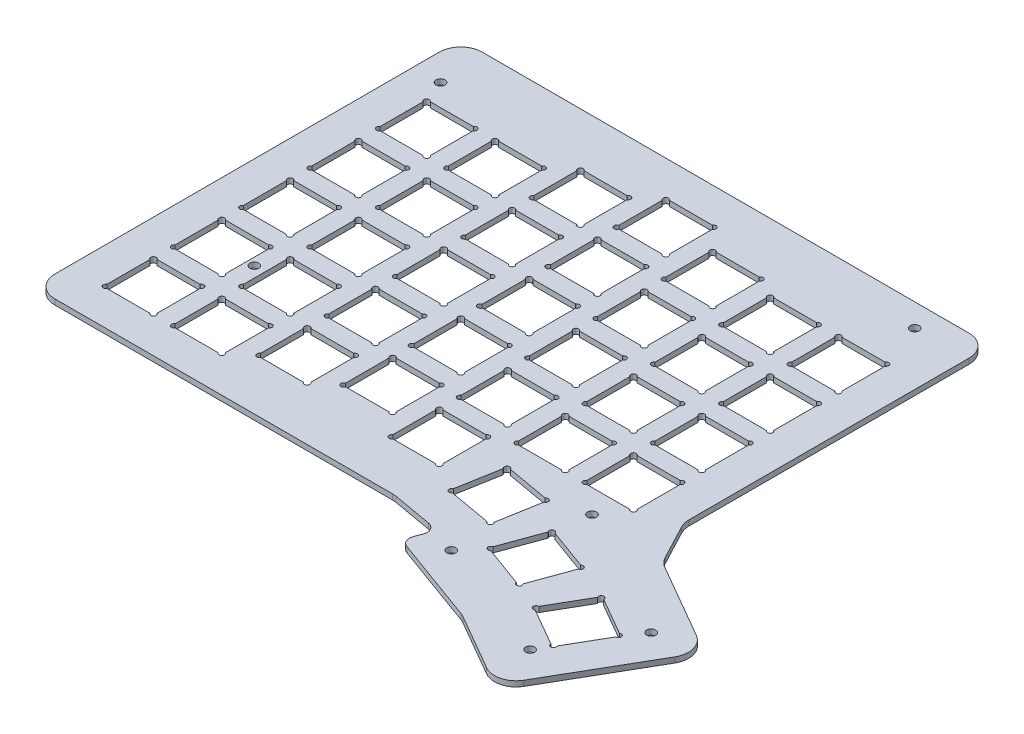
SolidWorks part; units mm, degrees
ref_plane "Front Plane" through (0, 0, 0) normal (0, 0, 1) x (1, 0, 0)
ref_plane "Top Plane" through (0, 0, 0) normal (0, 1, 0) x (1, 0, 0)
ref_plane "Right Plane" through (0, 0, 0) normal (1, 0, 0) x (0, 0, -1)
sketch "Sketch1" plane through (0, 0, 0) normal (0, 1, 0) x (1, 0, 0)
  line L0 (-118.7762, 124.6491) -> (29.0238, 124.6491)
  line L3 (35.6333, 26.5266) -> (63.1524, 10.6384)
  line L4 (63.1524, 10.6384) -> (41.7463, -26.4382)
  line L5 (41.7463, -26.4382) -> (20.3874, -14.1066)
  line L6 (20.3874, -14.1066) -> (-6.2441, -4.4135)
  line L7 (-6.2441, -4.4135) -> (-3.5838, 2.8955)
  line L8 (-3.5838, 2.8955) -> (-18.0659, 5.4491)
  line L9 (-18.0659, 5.4491) -> (-118.7762, 5.4491)
  line L10 (-118.7762, 5.4491) -> (-118.7762, 124.6491)
  line L11 (-17.8035, 8.4491) -> (-111.5762, 8.4491) construction
  line L12 (35.6333, 26.5266) -> (29.0238, 39.0847)
  line L13 (29.0238, 39.0847) -> (29.0238, 124.6491)
  line L14 (36.711, -20.067) -> (21.6594, -11.3769) construction
  line L15 (28.8016, 30.5418) -> (32.8015, 22.9418) construction
  line L16 (-115.7762, 12.6491) -> (-115.7762, 117.4491) construction
  line L17 (56.9174, 5.8389) -> (42.5399, -19.0636) construction
  line L18 (-111.5762, 121.6491) -> (22.8238, 121.6491) construction
  line L19 (30.0238, 26.4491) -> (55.6238, 11.5491) construction
  line L20 (26.0238, 118.4491) -> (26.0239, 34.0491) construction
  line L21 (26.0239, 34.0491) -> (30.0238, 26.4491) construction
  line L29 (21.6594, -11.3769) -> (1.2238, -3.9509) construction
  dimension "D9" = 3
  dimension "D4" = 3
  dimension "D7" = 20
  dimension "D5" = 10
  dimension "D8" = 30
  dimension "D3" = 3
  dimension "D2" = 3
  dimension "D10" = 3
  dimension "D11" = 3
  dimension "D6" = 3
  dimension "D12" = 3
  dimension "D13" = 3
  dimension "D14" = 5
  dimension "D15" = 3
extrude "Boss-Extrude1" add sketch "Sketch1" against normal blind 1.5
sketch "Sketch2" plane through (0, 0, 0) normal (0, 1, 0) x (1, 0, 0)
  line L0 (-37.8882, 114.9491) -> (-51.8882, 100.9491) construction
  line L1 (-51.8882, 114.9491) -> (-37.8882, 114.9491)
  line L2 (-51.8882, 114.9491) -> (-51.8882, 100.9491)
  line L3 (-51.8882, 100.9491) -> (-37.8882, 100.9491)
  line L4 (-37.8882, 114.9491) -> (-37.8882, 100.9491)
  line L5 (-51.8882, 114.9491) -> (-37.8882, 100.9491) construction
  line L6 (29.0238, 124.6491) -> (-118.7762, 124.6491) construction
  line L7 (-118.7762, 124.6491) -> (-118.7762, 5.4491) construction
  line L8 (-51.8882, 114.9491) -> (-52.065, 115.1259) construction
  line L9 (-51.5346, 114.5956) -> (-51.8882, 113.9341) construction
  line L10 (-51.5346, 114.5956) -> (-50.8732, 114.9491) construction
  circle A0 centre (-38.2418, 114.5956) radius 0.75
  circle A1 centre (-51.5346, 114.5956) radius 0.75
  circle A2 centre (-51.7114, 101.1259) radius 0.75
  circle A3 centre (-38.2418, 101.3027) radius 0.75
  dimension "D5" = 1.5
  dimension "D7" = 1.5
  dimension "D9" = 1.5
  dimension "D11" = 1.5
  dimension "D1" = 14
  dimension "D3" = 9.7
  dimension "D2" = 66.888
  dimension "D4" = 0.5
  dimension "D6" = 0.5
  dimension "D8" = 0.25
  dimension "D10" = 0.5
extrude "Cut-Extrude1" cut sketch "Sketch2" against normal blind 10 contours A3 L4 A0 L1 A1 L2 A2 L3 | A1 | A0 | A3 | A2 region at (-44.8994, 0, -107.9379)
sketch "Sketch3" plane through (0, 0, 0) normal (0, 1, 0) x (1, 0, 0)
  line L0 (-38.9032, 114.9491) -> (-50.8732, 114.9491) construction
  line L1 (-70.9383, 110.1866) -> (-56.9381, 110.1866)
  line L2 (-70.9383, 110.1866) -> (-70.9383, 96.1865)
  line L3 (-70.9383, 96.1865) -> (-56.9381, 96.1865)
  line L4 (-56.9381, 110.1866) -> (-56.9381, 96.1865)
  line L5 (-70.9383, 110.1866) -> (-56.9381, 96.1865) construction
  line L7 (-56.9381, 110.1866) -> (-70.9383, 96.1865) construction
  line L8 (-51.8882, 107.8944) -> (-37.8882, 107.9491) construction
  line L9 (-51.8882, 113.9341) -> (-51.8882, 101.8548) construction
  line L10 (-37.8882, 113.9341) -> (-37.8882, 101.9641) construction
  circle A0 centre (-57.2917, 109.8331) radius 0.75
  circle A1 centre (-70.5847, 109.8331) radius 0.75
  circle A2 centre (-70.5847, 96.5401) radius 0.75
  circle A3 centre (-57.2917, 96.5401) radius 0.75
  point P6 (-44.8882, 114.9491)
  point P7 (-63.9382, 110.1866)
  dimension "D7" = 1.5
  dimension "D9" = 1.5
  dimension "D4" = 0.5
  dimension "D6" = 0.5
  dimension "D8" = 1.5
  dimension "D10" = 1.5
  dimension "D1" = 19.05
  dimension "D2" = 4.7625
  dimension "D3" = 0.5
  dimension "D5" = 0.5
sketch "Sketch4" plane through (0, 0, 0) normal (0, 1, 0) x (1, 0, 0)
  line L0 (-38.9032, 114.9491) -> (-50.8732, 114.9491) construction
  line L1 (-89.9883, 105.4241) -> (-75.9881, 105.4241)
  line L2 (-89.9883, 105.4241) -> (-89.9883, 91.424)
  line L3 (-89.9883, 91.424) -> (-75.9881, 91.424)
  line L4 (-75.9881, 105.4241) -> (-75.9881, 91.424)
  line L5 (-56.9381, 110.1866) -> (-56.9381, 96.1865) construction
  line L6 (-89.9883, 105.4241) -> (-75.9881, 91.424) construction
  line L7 (-75.9881, 105.4241) -> (-89.9883, 91.424) construction
  line L8 (-51.8882, 107.8944) -> (-37.8882, 107.9491) construction
  line L9 (-51.8882, 113.9341) -> (-51.8882, 101.8548) construction
  line L10 (-37.8882, 113.9341) -> (-37.8882, 101.9641) construction
  circle A0 centre (-76.3417, 105.0706) radius 0.75
  circle A1 centre (-89.6347, 105.0706) radius 0.75
  circle A2 centre (-89.6347, 91.7776) radius 0.75
  circle A3 centre (-76.3417, 91.7776) radius 0.75
  dimension "D7" = 1.5
  dimension "D9" = 1.5
  dimension "D4" = 0.5
  dimension "D6" = 0.5
  dimension "D8" = 1.5
  dimension "D10" = 1.5
  dimension "D3" = 0.5
  dimension "D5" = 0.5
  dimension "D1" = 9.525
  dimension "D2" = 19.05
sketch "Sketch5" plane through (0, 0, 0) normal (0, 1, 0) x (1, 0, 0)
  line L0 (-38.9032, 114.9491) -> (-50.8732, 114.9491) construction
  line L1 (-109.0383, 105.4241) -> (-95.0381, 105.4241)
  line L2 (-109.0383, 105.4241) -> (-109.0383, 91.424)
  line L3 (-109.0383, 91.424) -> (-95.0381, 91.424)
  line L4 (-95.0381, 105.4241) -> (-95.0381, 91.424)
  line L5 (-75.9881, 105.4241) -> (-75.9881, 91.424) construction
  line L6 (-109.0383, 105.4241) -> (-95.0381, 91.424) construction
  line L8 (-95.0381, 105.4241) -> (-109.0383, 91.424) construction
  line L9 (-51.8882, 107.8944) -> (-37.8882, 107.9491) construction
  line L10 (-51.8882, 113.9341) -> (-51.8882, 101.8548) construction
  line L11 (-37.8882, 113.9341) -> (-37.8882, 101.9641) construction
  circle A0 centre (-108.6847, 105.0706) radius 0.75
  circle A1 centre (-95.3917, 105.0706) radius 0.75
  circle A2 centre (-95.3917, 91.7776) radius 0.75
  circle A3 centre (-108.6847, 91.7776) radius 0.75
  dimension "D7" = 1.5
  dimension "D9" = 1.5
  dimension "D4" = 0.5
  dimension "D6" = 0.5
  dimension "D8" = 1.5
  dimension "D10" = 1.5
  dimension "D1" = 19.05
  dimension "D3" = 0.5
  dimension "D5" = 0.5
  dimension "D2" = 9.525
sketch "Sketch6" plane through (0, 0, 0) normal (0, 1, 0) x (1, 0, 0)
  line L0 (-38.9032, 114.9491) -> (-50.8732, 114.9491) construction
  line L1 (-32.8382, 108.9491) -> (-18.8381, 108.9491)
  line L2 (-32.8382, 108.9491) -> (-32.8382, 94.949)
  line L3 (-32.8382, 94.949) -> (-18.8381, 94.949)
  line L4 (-18.8381, 108.9491) -> (-18.8381, 94.949)
  line L5 (-51.8882, 113.9341) -> (-51.8882, 101.8548) construction
  line L6 (-32.8382, 108.9491) -> (-18.8381, 94.949) construction
  line L7 (-18.8381, 108.9491) -> (-32.8382, 94.949) construction
  line L8 (-51.8882, 107.8944) -> (-37.8882, 107.9491) construction
  line L9 (-51.8882, 113.9341) -> (-51.8882, 101.8548) construction
  line L10 (-37.8882, 113.9341) -> (-37.8882, 101.9641) construction
  circle A0 centre (-32.4846, 108.5956) radius 0.75
  circle A1 centre (-19.1916, 108.5956) radius 0.75
  circle A2 centre (-32.4846, 95.3026) radius 0.75
  circle A3 centre (-19.1916, 95.3026) radius 0.75
  dimension "D7" = 1.5
  dimension "D9" = 1.5
  dimension "D4" = 0.5
  dimension "D6" = 0.5
  dimension "D8" = 1.5
  dimension "D10" = 1.5
  dimension "D3" = 0.5
  dimension "D5" = 0.5
  dimension "D2" = 19.05
  dimension "D1" = 6
sketch "Sketch7" plane through (0, 0, 0) normal (0, 1, 0) x (1, 0, 0)
  line L0 (-38.9032, 114.9491) -> (-50.8732, 114.9491) construction
  line L1 (-13.7882, 105.9491) -> (0.2119, 105.9491)
  line L2 (-13.7882, 105.9491) -> (-13.7882, 91.949)
  line L3 (-13.7882, 91.949) -> (0.2119, 91.949)
  line L4 (0.2119, 105.9491) -> (0.2119, 91.949)
  line L5 (-32.8382, 108.9491) -> (-32.8382, 94.949) construction
  line L6 (-13.7882, 105.9491) -> (0.2119, 91.949) construction
  line L7 (0.2119, 105.9491) -> (-13.7882, 91.949) construction
  line L8 (-51.8882, 107.8944) -> (-37.8882, 107.9491) construction
  line L9 (-51.8882, 113.9341) -> (-51.8882, 101.8548) construction
  line L10 (-37.8882, 113.9341) -> (-37.8882, 101.9641) construction
  circle A0 centre (-13.4346, 105.5956) radius 0.75
  circle A1 centre (-0.1416, 105.5956) radius 0.75
  circle A2 centre (-0.1416, 92.3026) radius 0.75
  circle A3 centre (-13.4346, 92.3026) radius 0.75
  dimension "D7" = 1.5
  dimension "D9" = 1.5
  dimension "D4" = 0.5
  dimension "D6" = 0.5
  dimension "D8" = 1.5
  dimension "D10" = 1.5
  dimension "D3" = 0.5
  dimension "D5" = 0.5
  dimension "D2" = 19.05
  dimension "D1" = 9
sketch "Sketch8" plane through (0, 0, 0) normal (0, 1, 0) x (1, 0, 0)
  line L0 (-38.9032, 114.9491) -> (-50.8732, 114.9491) construction
  line L1 (5.2618, 105.9491) -> (19.2619, 105.9491)
  line L2 (5.2618, 105.9491) -> (5.2618, 91.949)
  line L3 (5.2618, 91.949) -> (19.2619, 91.949)
  line L4 (19.2619, 105.9491) -> (19.2619, 91.949)
  line L5 (-13.7882, 105.9491) -> (-13.7882, 91.949) construction
  line L6 (5.2618, 105.9491) -> (19.2619, 91.949) construction
  line L7 (19.2619, 105.9491) -> (5.2618, 91.949) construction
  line L8 (-51.8882, 107.8944) -> (-37.8882, 107.9491) construction
  line L9 (-51.8882, 113.9341) -> (-51.8882, 101.8548) construction
  line L10 (-37.8882, 113.9341) -> (-37.8882, 101.9641) construction
  circle A0 centre (5.6154, 105.5956) radius 0.75
  circle A1 centre (18.9084, 105.5956) radius 0.75
  circle A2 centre (18.9084, 92.3026) radius 0.75
  circle A3 centre (5.6154, 92.3026) radius 0.75
  dimension "D7" = 1.5
  dimension "D9" = 1.5
  dimension "D4" = 0.5
  dimension "D6" = 0.5
  dimension "D8" = 1.5
  dimension "D10" = 1.5
  dimension "D1" = 19.05
  dimension "D3" = 0.5
  dimension "D5" = 0.5
  dimension "D2" = 9
extrude "Cut-Extrude2" cut sketch "Sketch3" against normal blind 10 contours L1 L4 L3 L2 | A0 | A1 | A2 | A3
extrude "Cut-Extrude3" cut sketch "Sketch4" against normal blind 10 contours A3 L4 A0 L1 A1 L2 A2 L3 | A0 | A1 | A2 | A3 region at (-82.9882, 0, -98.4241)
extrude "Cut-Extrude4" cut sketch "Sketch5" against normal blind 10 contours A3 L3 A2 L4 A1 L1 A0 L2 | A1 | A0 | A3 | A2 region at (-102.0382, 0, -98.4241)
extrude "Cut-Extrude5" cut sketch "Sketch6" against normal blind 10 contours L1 L4 L3 L2 | A0 | A1 | A2 | A3
extrude "Cut-Extrude6" cut sketch "Sketch7" against normal blind 10 contours L1 L4 L3 L2 | A0 | A1 | A3 | A2
extrude "Cut-Extrude7" cut sketch "Sketch8" against normal blind 10 contours L2 A0 L1 | L1 L4 L3 L2 | A1 | A3 | A2 | A0 region at (5.7699, 0, -105.441)
pattern_linear "LPattern1" count 5 spacing 19.05 along (0, 0, 1) of "Cut-Extrude5", "Cut-Extrude1", "Cut-Extrude2", "Cut-Extrude3", "Cut-Extrude4"
pattern_linear "LPattern2" count 4 spacing 19.05 along (0, 0, 1) of "Cut-Extrude7", "Cut-Extrude6"
sketch "Sketch10" plane through (0, 0, 0) normal (0, 1, 0) x (1, 0, 0)
  line L0 (-34.8381, 34.7491) -> (-16.8381, 34.7491) construction
  line L1 (-16.8381, 34.7491) -> (-16.8381, 16.7491) construction
  line L2 (-16.8381, 16.7491) -> (-34.8381, 16.7491) construction
  line L3 (-34.8381, 16.7491) -> (-34.8381, 34.7491) construction
  line L4 (-15.7881, 50.7991) -> (2.2119, 50.7991) construction
  line L5 (2.2119, 50.7991) -> (2.2119, 32.7991) construction
  line L6 (2.2119, 32.7991) -> (-15.7881, 32.7991) construction
  line L7 (-15.7881, 32.7991) -> (-15.7881, 50.7991) construction
  line L8 (-31.8232, 32.7491) -> (-19.8531, 32.7491) construction
  line L9 (-32.8382, 31.7341) -> (-32.8382, 19.764) construction
  line L10 (-12.7732, 48.7991) -> (-0.8031, 48.7991) construction
  line L11 (-13.7882, 47.7841) -> (-13.7882, 35.814) construction
  line L12 (-9.0902, 27.9822) -> (4.6972, 25.5511)
  line L13 (-9.0902, 27.9822) -> (-11.5213, 14.1948)
  line L14 (4.6972, 25.5511) -> (2.2661, 11.7637)
  line L15 (-11.5213, 14.1948) -> (2.2661, 11.7637)
  line L16 (-9.0902, 27.9822) -> (2.2661, 11.7637) construction
  line L17 (4.6972, 25.5511) -> (-11.5213, 14.1948) construction
  line L18 (-51.8882, 107.8944) -> (-37.8882, 107.9491) construction
  line L19 (-51.8882, 113.9341) -> (-51.8882, 101.8548) construction
  line L21 (-31.8232, 18.749) -> (-19.8531, 18.749) construction
  line L22 (-37.8882, 113.9341) -> (-37.8882, 101.9641) construction
  line L23 (-13.8381, 12.5725) -> (-10.7125, 30.2991) construction
  line L24 (-10.7125, 30.2991) -> (7.0141, 27.1734) construction
  line L25 (7.0141, 27.1734) -> (3.8884, 9.4469) construction
  line L26 (3.8884, 9.4469) -> (-13.8381, 12.5725) construction
  line L27 (-10.3058, 21.0885) -> (-12.2753, 21.4358) construction
  line L28 (-2.1965, 26.7667) -> (-1.8492, 28.7362) construction
  circle A0 centre (-8.8034, 27.5726) radius 0.75
  circle A1 centre (4.2876, 25.2643) radius 0.75
  circle A2 centre (-11.1117, 14.4816) radius 0.75
  circle A3 centre (1.9793, 12.1733) radius 0.75
  point P10 (-25.8381, 32.7491)
  point P11 (-25.8381, 34.7491)
  point P14 (-32.8382, 25.7491)
  point P15 (-34.8381, 25.7491)
  point P18 (-6.7881, 48.7991)
  point P19 (-6.7881, 50.7991)
  point P22 (-13.7882, 41.7991)
  point P23 (-15.7881, 41.7991)
  dimension "D11" = 1.5
  dimension "D10" = 0.5
  dimension "D6" = 2.5
  dimension "D1" = 18
  dimension "D2" = 10
  dimension "D3" = 90
  dimension "D4" = 90
  dimension "D5" = 3
  dimension "D7" = 0.5
  dimension "D8" = 0.5
  dimension "D9" = 0.5
extrude "Cut-Extrude8" cut sketch "Sketch10" against normal blind 10 contours L12 L14 L15 L13 | A0 | A1 | A2 | A3
sketch "Sketch11" plane through (0, 0, 0) normal (0, 1, 0) x (1, 0, 0)
  line L4 (12.9973, 25.7019) -> (29.9117, 19.5455) construction
  line L5 (12.9973, 25.7019) -> (3.7627, 0.3302) construction
  line L6 (29.9117, 19.5455) -> (20.6772, -5.8262) construction
  line L7 (3.7627, 0.3302) -> (20.6772, -5.8262) construction
  line L8 (12.6535, 18.9099) -> (21.021, 0.9658) construction
  line L9 (25.8093, 14.1216) -> (7.8652, 5.7541) construction
  line L10 (-10.7125, 30.2991) -> (7.0141, 27.1734) construction
  line L11 (7.0141, 27.1734) -> (3.8884, 9.4469) construction
  line L12 (3.8884, 9.4469) -> (-13.8381, 12.5725) construction
  line L13 (-13.8381, 12.5725) -> (-10.7125, 30.2991) construction
  line L14 (-8.0906, 27.806) -> (3.6976, 25.7274) construction
  line L15 (-9.2665, 26.9826) -> (-11.345, 15.1944) construction
  line L16 (-2.1965, 26.7667) -> (-1.8492, 28.7362) construction
  line L17 (-10.3058, 21.0885) -> (-12.2753, 21.4358) construction
  line L18 (-51.8882, 107.8944) -> (-37.8882, 107.9491) construction
  line L19 (-51.8882, 113.9341) -> (-51.8882, 101.8548) construction
  line L20 (12.6535, 18.9099) -> (25.8093, 14.1216)
  line L21 (25.8093, 14.1216) -> (21.021, 0.9658)
  line L22 (21.021, 0.9658) -> (7.8652, 5.7541)
  line L23 (7.8652, 5.7541) -> (12.6535, 18.9099)
  line L24 (-31.8232, 18.749) -> (-19.8531, 18.749) construction
  line L25 (10.2593, 12.332) -> (8.38, 13.016) construction
  line L26 (19.2314, 16.5157) -> (21.4545, 22.6237) construction
  line L32 (-37.8882, 113.9341) -> (-37.8882, 101.9641) construction
  line L39 (3.7627, 0.3302) -> (20.6772, -5.8262) construction
  circle A0 centre (12.8648, 18.4567) radius 0.75
  circle A1 centre (25.3561, 13.9103) radius 0.75
  circle A2 centre (20.8097, 1.4189) radius 0.75
  circle A3 centre (8.3183, 5.9654) radius 0.75
  arc A4 (4.521, 24.5515) -> (3.6976, 25.7274) centre (4.2876, 25.2643) ccw construction
  dimension "D1" = 18
  dimension "D4" = 90
  dimension "D2" = 90
  dimension "D3" = 90
  dimension "D5" = 20
  dimension "D6" = 90
  dimension "D7" = 90
  dimension "D8" = 27
  dimension "D9" = 3
  dimension "D10" = 27
  dimension "D11" = 0.5
  dimension "D12" = 0.5
  dimension "D13" = 0.5
  dimension "D14" = 0.5
sketch "Sketch12" plane through (0, 0, 0) normal (0, 1, 0) x (1, 0, 0)
  line L0 (35.4783, 9.9013) -> (47.6027, 2.9013)
  line L1 (47.6027, 2.9013) -> (40.6027, -9.2232)
  line L2 (40.6027, -9.2232) -> (28.4782, -2.2231)
  line L3 (28.4782, -2.2231) -> (35.4783, 9.9013)
  line L5 (35.4783, 9.9013) -> (40.6027, -9.2232) construction
  line L6 (-118.7762, 5.4491) -> (-18.0659, 5.4491) construction
  line L7 (3.7627, 0.3302) -> (20.6772, -5.8262) construction
  line L8 (20.6772, -5.8262) -> (101.0446, -35.0775) construction
  line L9 (23.4963, -6.8522) -> (36.9963, 16.5304)
  line L10 (36.9963, 16.5304) -> (52.5847, 7.5304)
  line L11 (52.5847, 7.5304) -> (39.0847, -15.8522)
  line L12 (39.0847, -15.8522) -> (23.4963, -6.8522)
  line L13 (41.5405, 6.4013) -> (44.7905, 12.0304) construction
  line L14 (31.9783, 3.8391) -> (30.2463, 4.8391) construction
  line L15 (29.9117, 19.5455) -> (20.6772, -5.8262) construction
  line L16 (12.9973, 25.7019) -> (29.9117, 19.5455) construction
  line L17 (47.6027, 2.9013) -> (28.4782, -2.2231) construction
  line L18 (-51.8882, 107.8944) -> (-37.8882, 107.9491) construction
  line L19 (-51.8882, 113.9341) -> (-51.8882, 101.8548) construction
  line L20 (-37.8882, 113.9341) -> (-37.8882, 101.9641) construction
  circle A0 centre (35.6077, 9.4184) radius 0.75
  circle A1 centre (47.1198, 2.7719) radius 0.75
  circle A2 centre (40.4733, -8.7402) radius 0.75
  circle A3 centre (28.9612, -2.0937) radius 0.75
  arc A4 (1.2665, 11.94) -> (2.4424, 12.7633) centre (1.9793, 12.1733) ccw construction
  dimension "D6" = 0.5
  dimension "D5" = 0.5
  dimension "D3" = 90
  dimension "D7" = 0.5
  dimension "D8" = 0.5
  dimension "D1" = 30
  dimension "D2" = 90
  dimension "D4" = 3
extrude "Cut-Extrude10" cut sketch "Sketch11" against normal blind 10 contours L20 L21 L22 L23 | A0 | A1 | A3 | A2
extrude "Cut-Extrude11" cut sketch "Sketch12" against normal blind 10 contours L0 L1 L2 L3 | A0 | A1 | A3 | A2
fillet "Fillet5" radius 6 9 edges at (29.0238, -0.75, -39.0847) (35.6333, -0.75, -26.5266) (63.1524, -0.75, -10.6384) (41.7463, -0.75, 26.4382) (20.3874, -0.75, 14.1066) (-18.0659, -0.75, -5.4491) (-118.7762, -0.75, -5.4491) (-118.7762, -0.75, -124.6491) (29.0238, -0.75, -124.6491)
fillet "Fillet6" radius 2.5 2 edges at (-3.5838, -0.75, -2.8955) (-6.2441, -0.75, 4.4135)
sketch "Sketch50" plane through (0, -1.5, 0) normal (0, -1, 0) x (-1, 0, 0)
  circle A0 centre (111.2762, 111.5152) radius 1.25
  circle A3 centre (-14.2238, 118.2491) radius 1.25
  circle A5 centre (92.9762, 41.2831) radius 1.25
  circle A9 centre (-14.2238, 28.2491) radius 1.25
  circle A11 centre (-50.9898, 7.9991) radius 1.25
  circle A13 centre (-38.2238, -13.0009) radius 1.25
  circle A15 centre (-3.2398, -0.0009) radius 1.25
  dimension "D1" = 2.5
  dimension "D4" = 2.5
  dimension "D6" = 2.5
  dimension "D10" = 2.5
  dimension "D12" = 2.5
  dimension "D14" = 2.5
  dimension "D16" = 2.5
extrude "Cut-Extrude18" cut sketch "Sketch50" against normal blind 10
equation "\"EDGE_PAD\"=3"
equation "\"LAYER_SWITCH_THICKNESS\"= 1.5"
equation "\"D1@Boss-Extrude1\"=\"LAYER_SWITCH_THICKNESS\""
equation "\"CUTOUT_SIZE\"= 14"
equation "\"D1@Sketch2\"=\"CUTOUT_SIZE\""
equation "\"D2@Sketch2\"=\"EDGE_PAD\"+63.888"
equation "\"D3@Sketch2\"=\"EDGE_PAD\"+6.7"
equation "\"CASE_THICKNESS\"= 3"
equation "\"SCREW_SIZE\"= 2.5"
equation "\"OUTER_SCREW_SIZE\"=2.5"
equation "\"D1@Sketch50\"=\"OUTER_SCREW_SIZE\""
equation "\"D4@Sketch50\"=\"OUTER_SCREW_SIZE\""
equation "\"D6@Sketch50\"=\"OUTER_SCREW_SIZE\""
equation "\"D10@Sketch50\"=\"OUTER_SCREW_SIZE\""
equation "\"D12@Sketch50\"=\"OUTER_SCREW_SIZE\""
equation "\"D14@Sketch50\"=\"OUTER_SCREW_SIZE\""
equation "\"D16@Sketch50\"=\"OUTER_SCREW_SIZE\""
equation "\"EDGE_CIRCLES\"= 1.5"
equation "\"EDGE_CIRCLES_OFFSET\"= 0.5"
equation "\"D4@Sketch2\"=\"EDGE_CIRCLES_OFFSET\""
equation "\"D5@Sketch2\"=\"EDGE_CIRCLES\""
equation "\"D6@Sketch2\"=\"EDGE_CIRCLES_OFFSET\""
equation "\"D7@Sketch2\"=\"EDGE_CIRCLES\""
equation "\"D10@Sketch2\"=\"EDGE_CIRCLES_OFFSET\""
equation "\"D11@Sketch2\"=\"EDGE_CIRCLES\""
equation "\"D9@Sketch2\"=\"EDGE_CIRCLES\""
equation "\"D3@Sketch3\"=\"EDGE_CIRCLES_OFFSET\""
equation "\"D4@Sketch3\"=\"EDGE_CIRCLES_OFFSET\""
equation "\"D5@Sketch3\"=\"EDGE_CIRCLES_OFFSET\""
equation "\"D6@Sketch3\"=\"EDGE_CIRCLES_OFFSET\""
equation "\"D7@Sketch3\"=\"EDGE_CIRCLES\""
equation "\"D8@Sketch3\"=\"EDGE_CIRCLES\""
equation "\"D9@Sketch3\"=\"EDGE_CIRCLES\""
equation "\"D10@Sketch3\"=\"EDGE_CIRCLES\""
equation "\"D3@Sketch4\"=\"EDGE_CIRCLES_OFFSET\""
equation "\"D4@Sketch4\"=\"EDGE_CIRCLES_OFFSET\""
equation "\"D5@Sketch4\"=\"EDGE_CIRCLES_OFFSET\""
equation "\"D6@Sketch4\"=\"EDGE_CIRCLES_OFFSET\""
equation "\"D7@Sketch4\"=\"EDGE_CIRCLES\""
equation "\"D8@Sketch4\"=\"EDGE_CIRCLES\""
equation "\"D9@Sketch4\"=\"EDGE_CIRCLES\""
equation "\"D10@Sketch4\"=\"EDGE_CIRCLES\""
equation "\"D3@Sketch5\"=\"EDGE_CIRCLES_OFFSET\""
equation "\"D4@Sketch5\"=\"EDGE_CIRCLES_OFFSET\""
equation "\"D5@Sketch5\"=\"EDGE_CIRCLES_OFFSET\""
equation "\"D6@Sketch5\"=\"EDGE_CIRCLES_OFFSET\""
equation "\"D7@Sketch5\"=\"EDGE_CIRCLES\""
equation "\"D8@Sketch5\"=\"EDGE_CIRCLES\""
equation "\"D9@Sketch5\"=\"EDGE_CIRCLES\""
equation "\"D10@Sketch5\"=\"EDGE_CIRCLES\""
equation "\"D3@Sketch6\"=\"EDGE_CIRCLES_OFFSET\""
equation "\"D4@Sketch6\"=\"EDGE_CIRCLES_OFFSET\""
equation "\"D5@Sketch6\"=\"EDGE_CIRCLES_OFFSET\""
equation "\"D6@Sketch6\"=\"EDGE_CIRCLES_OFFSET\""
equation "\"D7@Sketch6\"=\"EDGE_CIRCLES\""
equation "\"D8@Sketch6\"=\"EDGE_CIRCLES\""
equation "\"D9@Sketch6\"=\"EDGE_CIRCLES\""
equation "\"D10@Sketch6\"=\"EDGE_CIRCLES\""
equation "\"D3@Sketch7\"=\"EDGE_CIRCLES_OFFSET\""
equation "\"D4@Sketch7\"=\"EDGE_CIRCLES_OFFSET\""
equation "\"D5@Sketch7\"=\"EDGE_CIRCLES_OFFSET\""
equation "\"D6@Sketch7\"=\"EDGE_CIRCLES_OFFSET\""
equation "\"D7@Sketch7\"=\"EDGE_CIRCLES\""
equation "\"D8@Sketch7\"=\"EDGE_CIRCLES\""
equation "\"D9@Sketch7\"=\"EDGE_CIRCLES\""
equation "\"D10@Sketch7\"=\"EDGE_CIRCLES\""
equation "\"D3@Sketch8\"=\"EDGE_CIRCLES_OFFSET\""
equation "\"D4@Sketch8\"=\"EDGE_CIRCLES_OFFSET\""
equation "\"D5@Sketch8\"=\"EDGE_CIRCLES_OFFSET\""
equation "\"D6@Sketch8\"=\"EDGE_CIRCLES_OFFSET\""
equation "\"D7@Sketch8\"=\"EDGE_CIRCLES\""
equation "\"D8@Sketch8\"=\"EDGE_CIRCLES\""
equation "\"D9@Sketch8\"=\"EDGE_CIRCLES\""
equation "\"D10@Sketch8\"=\"EDGE_CIRCLES\""
equation "\"D7@Sketch10\"=\"EDGE_CIRCLES_OFFSET\""
equation "\"D8@Sketch10\"=\"EDGE_CIRCLES_OFFSET\""
equation "\"D9@Sketch10\"=\"EDGE_CIRCLES_OFFSET\""
equation "\"D10@Sketch10\"=\"EDGE_CIRCLES_OFFSET\""
equation "\"D11@Sketch10\"=\"EDGE_CIRCLES\""
equation "\"D11@Sketch11\"=\"EDGE_CIRCLES_OFFSET\""
equation "\"D12@Sketch11\"=\"EDGE_CIRCLES_OFFSET\""
equation "\"D13@Sketch11\"=\"EDGE_CIRCLES_OFFSET\""
equation "\"D14@Sketch11\"=\"EDGE_CIRCLES_OFFSET\""
equation "\"D5@Sketch12\"=\"EDGE_CIRCLES_OFFSET\""
equation "\"D6@Sketch12\"=\"EDGE_CIRCLES_OFFSET\""
equation "\"D7@Sketch12\"=\"EDGE_CIRCLES_OFFSET\""
equation "\"D8@Sketch12\"=\"EDGE_CIRCLES_OFFSET\""
equation "\"D15@Sketch1\"=\"EDGE_PAD\""
equation "\"D3@Sketch1\"=\"EDGE_PAD\""
equation "\"D9@Sketch1\"=\"EDGE_PAD\""
equation "\"D10@Sketch1\"=\"EDGE_PAD\""
equation "\"D11@Sketch1\"=\"EDGE_PAD\""
equation "\"D12@Sketch1\"=\"EDGE_PAD\""
equation "\"D6@Sketch1\"=\"EDGE_PAD\""
equation "\"D13@Sketch1\"=\"EDGE_PAD\""
equation "\"D14@Sketch1\"=\"EDGE_PAD\"+2"
equation "\"D2@Sketch1\"=\"EDGE_PAD\""
equation "\"D4@Sketch1\"=\"EDGE_PAD\""
